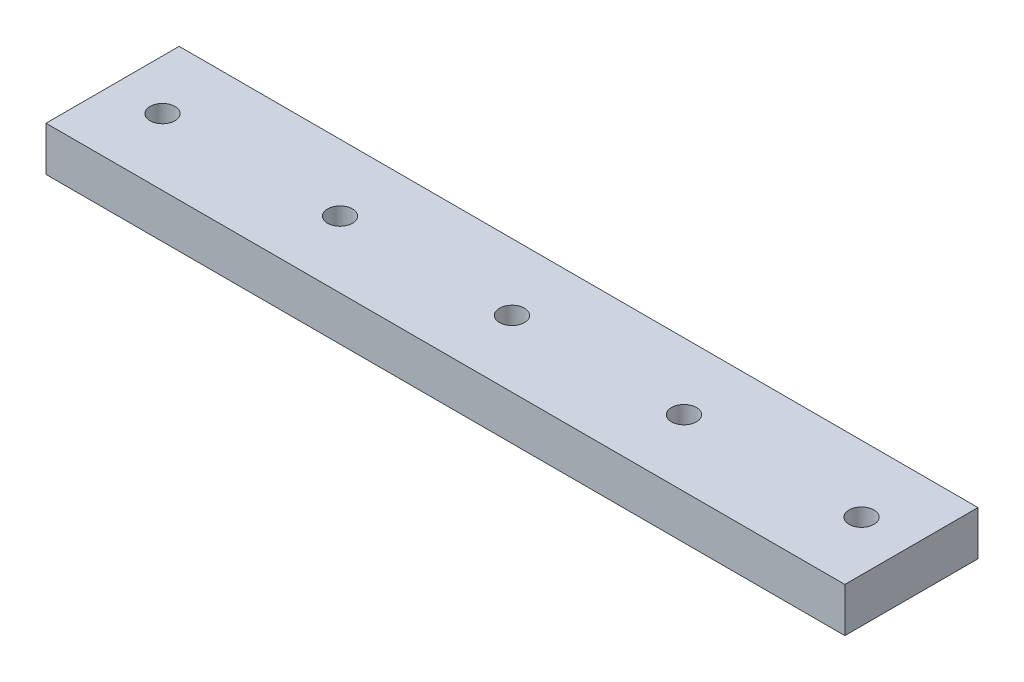
SolidWorks part; units mm, degrees
ref_plane "Front Plane" through (0, 0, 0) normal (0, 0, 1) x (1, 0, 0)
ref_plane "Top Plane" through (0, 0, 0) normal (0, 1, 0) x (1, 0, 0)
ref_plane "Right Plane" through (0, 0, 0) normal (1, 0, 0) x (0, 0, -1)
sketch "Sketch1" plane through (0, 0, 0) normal (0, 1, 0) x (1, 0, 0)
  line L0 (0, -19.05) -> (228.6, -19.05) construction
  line L1 (0, 0) -> (228.6, 0)
  line L2 (0, 0) -> (0, -38.1)
  line L3 (0, -38.1) -> (228.6, -38.1)
  line L4 (228.6, 0) -> (228.6, -38.1)
  circle A0 centre (14.2875, -19.05) radius 3.5719
  circle A1 centre (65.0875, -19.05) radius 3.5719
  circle A2 centre (114.3, -19.05) radius 3.5719
  circle A3 centre (163.5125, -19.05) radius 3.5719
  circle A4 centre (214.3125, -19.05) radius 3.5719
  point P17 (0, 0)
  point P18 (0, 0)
  point P19 (0, 0)
  point P20 (0, 0)
  point P21 (0, 0)
  dimension "D3" = 7.1437
  dimension "D1" = 38.1
  dimension "D2" = 228.6
  dimension "D4" = 14.2875
  dimension "D5" = 65.0875
  dimension "D6" = 114.3
  dimension "D7" = 163.5125
  dimension "D8" = 214.3125
extrude "Boss-Extrude1" add sketch "Sketch1" along normal blind 12.7
